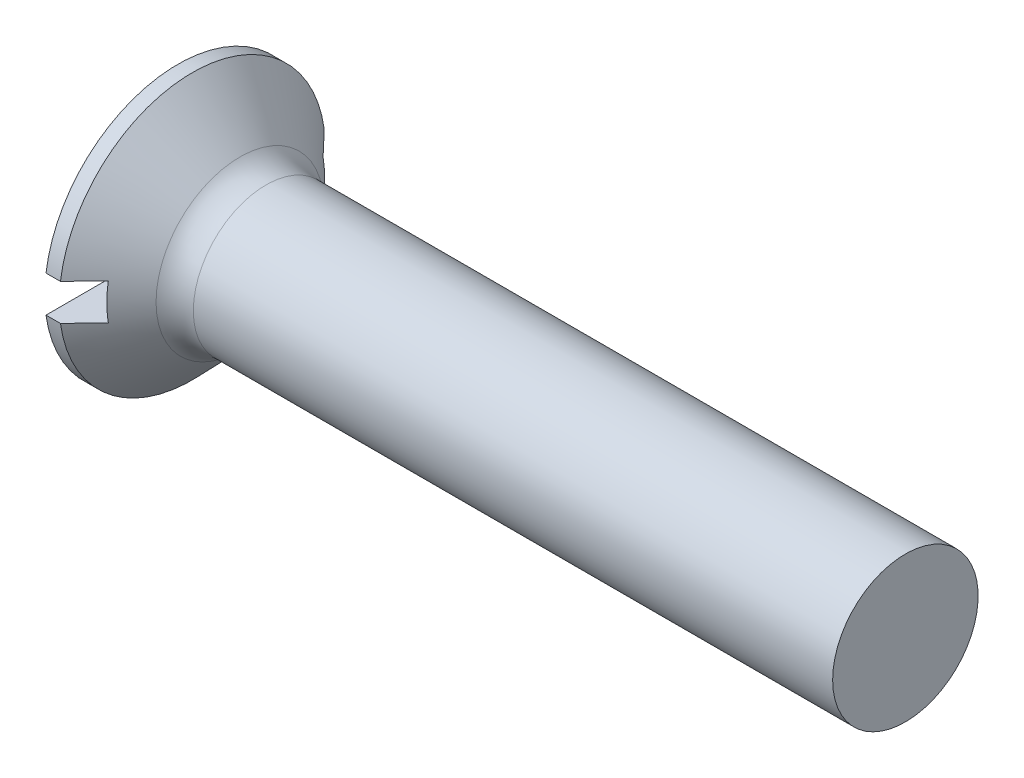
SolidWorks part; units mm, degrees
ref_plane "Front Plane" through (0, 0, 0) normal (0, 0, 1) x (1, 0, 0)
ref_plane "Top Plane" through (0, 0, 0) normal (0, 1, 0) x (1, 0, 0)
ref_plane "Right Plane" through (0, 0, 0) normal (1, 0, 0) x (0, 0, -1)
sketch "BodySke" plane through (0, 0, 0) normal (0, 0, 1) x (1, 0, 0)
  line L0 (0, 0) -> (111.3824, 0) construction
  line L1 (0, 0) -> (0, 9.15)
  line L2 (0, 9.15) -> (0.9924, 9.15)
  line L3 (0.9924, 9.15) -> (5, 5)
  line L4 (5, 5) -> (50, 5)
  line L5 (50, 5) -> (50, 0)
  line L6 (6.5, 8.824) -> (6.5, -5.8939) construction
  line L7 (0, 0) -> (50, 0)
  line L8 (8, 8.824) -> (8, -4.958) construction
  line L9 (0, -9.15) -> (0.9924, -9.15) construction
  line L10 (0.9924, -9.15) -> (5, -5) construction
  line L11 (5, -5) -> (50, -5) construction
  point P10 (50, 4.172)
  dimension "Thread_minor" = 8.344
  dimension "Length" = 50
  dimension "Head_height" = 5
  dimension "Head_dia" = 18.3
  dimension "Advance" = 1.5
revolve "BaseBody" add sketch "BodySke" angle 360 about L0
cosmetic thread "ThreadCosmetic" [suppressed] parameters "Thread_minor"=8.344
fillet "Fillet1" radius 2.5 1 edges at (5, 0, 5)
sketch "SlotSke" plane through (0, 0, 0) normal (-1, 0, 0) x (0, 0, 1)
  line L1 (-9.15, 1.25) -> (9.15, 1.25)
  line L2 (-9.15, 1.25) -> (-9.15, -1.25)
  line L3 (-9.15, -1.25) -> (9.15, -1.25)
  line L4 (9.15, 1.25) -> (9.15, -1.25)
  dimension "D1" = 18.3
  dimension "D2" = 9.15
  dimension "D3" = 1.25
extrude "Slot" cut sketch "SlotSke" against normal blind 2.6
sketch "ThdSchSke" plane through (0, 0, 0) normal (0, 0, 1) x (1, 0, 0)
  line L0 (0, 0) -> (55.1256, 0) construction
  line L1 (0, 0) -> (111.3824, 0) construction
  line L2 (49.522, 5) -> (49.522, 5.9561)
  line L3 (49.522, 5.9561) -> (50.478, 5.9561)
  line L4 (50.478, 5.9561) -> (50.478, 5)
  line L5 (50.478, 5) -> (50, 4.172)
  line L6 (50, 4.172) -> (49.522, 5)
  line L7 (5, 5) -> (50, 5) construction
  line L13 (50, 5) -> (50, 0) construction
revolve "ThreadSchematic" [suppressed] cut sketch "ThdSchSke" angle 360 about L0
pattern_linear "ThdSchPat" [suppressed] count 29 along (-1, 0, 0) of bodies 103
equation "\"Thread_minor@ThreadCosmetic\" = \"Thread_minor@BodySke\""
equation "\"D1@SlotSke\" = \"Head_dia@BodySke\""
equation "\"D2@SlotSke\" = \"D1@SlotSke\" / 2"
equation "\"D3@SlotSke\" = \"Slot_width@SlotSke\" / 2"
equation "\"Advance@ThdSchPat\" = \"Advance@BodySke\""
equation "\"D1@ThdSchPat\" =  int( ( \"Length@BodySke\" - \"Head_height@BodySke\" - \"Thread_runout@BodySke\" )  / \"Advance@ThdSchPat\" )   + 1"
